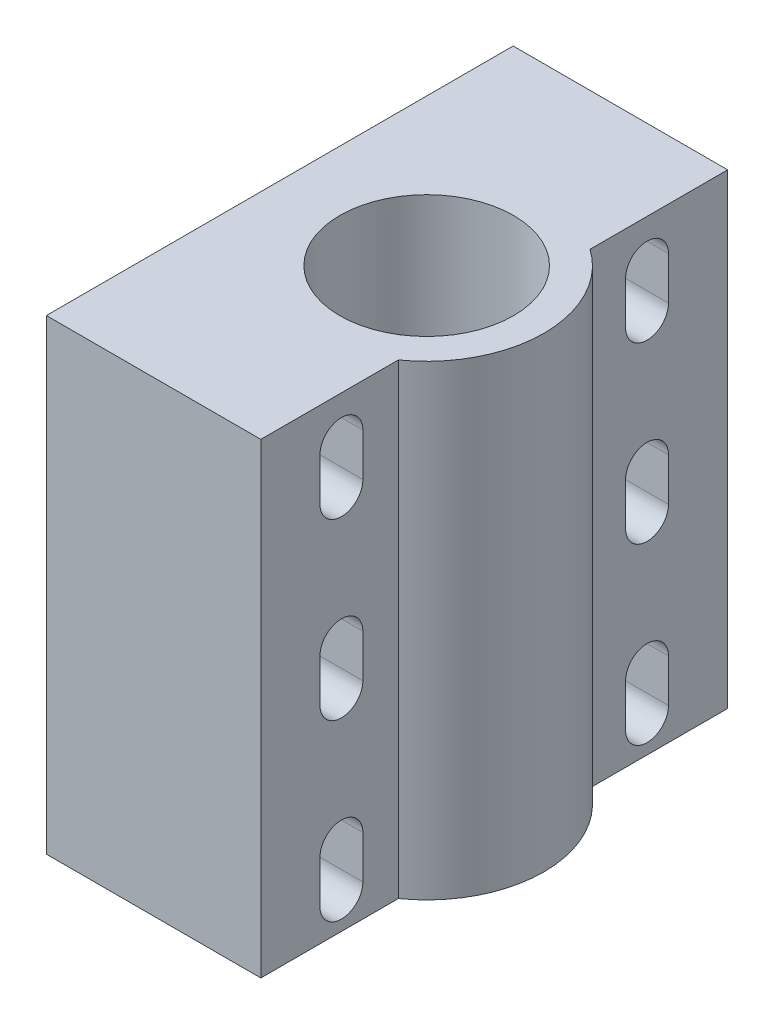
SolidWorks part; units mm, degrees
ref_plane "Front Plane" through (0, 0, 0) normal (0, 0, 1) x (1, 0, 0)
ref_plane "Top Plane" through (0, 0, 0) normal (0, 1, 0) x (1, 0, 0)
ref_plane "Right Plane" through (0, 0, 0) normal (1, 0, 0) x (0, 0, -1)
sketch "Sketch1" plane through (0, 0, 0) normal (0, 0, 1) x (1, 0, 0)
  line L0 (0, 0) -> (0, 6)
  line L1 (0, 6) -> (1.8335, 6)
  line L2 (1.8335, 6) -> (1.8335, 11.5)
  line L3 (1.8335, 11.5) -> (0, 11.5)
  line L4 (0, 11.5) -> (0, 15.5)
  line L5 (0, 15.5) -> (1.8335, 15.5)
  line L6 (1.8335, 15.5) -> (1.8335, 16.5)
  line L7 (-0.1665, 18.5) -> (-3, 18.5)
  line L8 (-3, 18.5) -> (-3, 0)
  line L9 (-3, 0) -> (0, 0)
  line L10 (7.9335, 6) -> (7.9335, 11.5) construction
  line L11 (1.8335, 16.5) -> (-0.1665, 18.5)
  point P9 (1.8335, 18.5)
  dimension "D1" = 5.5
  dimension "D2" = 4
  dimension "D3" = 6.1
  dimension "D4" = 6
  dimension "D5" = 3
  dimension "D6" = 3
revolve "Revolve1" add sketch "Sketch1" angle 360 about L10
sketch "Sketch2" plane through (0, 18.5, 0) normal (0, 1, 0) x (1, 0, 0)
  line L0 (-5.7665, -10.9335) -> (-5.7665, -21.7657)
  line L1 (-5.7665, 10.9335) -> (-5.7665, -10.9335)
  line L2 (-5.7665, -21.7657) -> (14.2335, -21.7657)
  line L3 (14.2335, 8.9359) -> (14.2335, 21.7657)
  line L5 (14.2335, -21.7657) -> (14.2335, -8.9359)
  line L6 (14.2335, 21.7657) -> (-5.7665, 21.7657)
  line L7 (-5.7665, 21.7657) -> (-5.7665, 10.9335)
  circle A1 centre (7.9335, 0) radius 8.1 construction
  arc A2 (14.2335, 8.9359) -> (14.2335, -8.9359) centre (7.9335, 0) ccw
  point P0 (-5.7665, 0)
  dimension "D1" = 13.7
  dimension "D2" = 20
extrude "Boss-Extrude1" add sketch "Sketch2" against normal up to surface (18.5 mm away) and the other way blind 25 up to face at (7.9335, 0, -7.9335)
sketch "Sketch3" plane through (-5.7665, 0, 0) normal (-1, 0, 0) x (0, 0, 1)
  line L0 (0, 43.5) -> (0, 0) construction
  line L1 (-21.7657, 43.5) -> (21.7657, 43.5) construction
  line L2 (21.7657, 0) -> (-21.7657, 0) construction
  line L3 (0, 37.5) -> (-14.25, 37.5) construction
  line L4 (0, 37.5) -> (14.25, 37.5) construction
  line L5 (-14.25, 39.5) -> (-14.25, 35.5) construction
  line L6 (-12.25, 39.5) -> (-12.25, 35.5)
  line L7 (-16.25, 39.5) -> (-16.25, 35.5)
  line L8 (14.25, 39.5) -> (14.25, 35.5) construction
  line L9 (16.25, 39.5) -> (16.25, 35.5)
  line L10 (12.25, 39.5) -> (12.25, 35.5)
  line L11 (-14.25, 23.25) -> (-14.25, 19.25) construction
  line L12 (-12.25, 23.25) -> (-12.25, 19.25)
  line L13 (-16.25, 23.25) -> (-16.25, 19.25)
  line L14 (14.25, 23.25) -> (14.25, 19.25) construction
  line L15 (16.25, 23.25) -> (16.25, 19.25)
  line L16 (12.25, 23.25) -> (12.25, 19.25)
  line L17 (-14.25, 7) -> (-14.25, 3) construction
  line L18 (-12.25, 7) -> (-12.25, 3)
  line L19 (-16.25, 7) -> (-16.25, 3)
  line L20 (14.25, 7) -> (14.25, 3) construction
  line L21 (16.25, 7) -> (16.25, 3)
  line L22 (12.25, 7) -> (12.25, 3)
  arc A0 (-12.25, 39.5) -> (-16.25, 39.5) centre (-14.25, 39.5) ccw
  arc A1 (-16.25, 35.5) -> (-12.25, 35.5) centre (-14.25, 35.5) ccw
  arc A2 (16.25, 39.5) -> (12.25, 39.5) centre (14.25, 39.5) ccw
  arc A3 (12.25, 35.5) -> (16.25, 35.5) centre (14.25, 35.5) ccw
  arc A4 (-12.25, 23.25) -> (-16.25, 23.25) centre (-14.25, 23.25) ccw
  arc A5 (-16.25, 19.25) -> (-12.25, 19.25) centre (-14.25, 19.25) ccw
  arc A6 (16.25, 23.25) -> (12.25, 23.25) centre (14.25, 23.25) ccw
  arc A7 (12.25, 19.25) -> (16.25, 19.25) centre (14.25, 19.25) ccw
  arc A8 (-12.25, 7) -> (-16.25, 7) centre (-14.25, 7) ccw
  arc A9 (-16.25, 3) -> (-12.25, 3) centre (-14.25, 3) ccw
  arc A10 (16.25, 7) -> (12.25, 7) centre (14.25, 7) ccw
  arc A11 (12.25, 3) -> (16.25, 3) centre (14.25, 3) ccw
  point P11 (-14.25, 37.5)
  point P17 (14.25, 37.5)
  point P27 (-14.25, 21.25)
  point P33 (14.25, 21.25)
  point P41 (-14.25, 5)
  point P47 (14.25, 5)
  dimension "D3" = 2
  dimension "D1" = 28.5
  dimension "D2" = 4
  dimension "D5" = 6
  dimension "D4" = 3
extrude "Cut-Extrude1" cut sketch "Sketch3" against normal blind 50
sketch "Sketch4" plane through (0, 18.5, 0) normal (0, 1, 0) x (1, 0, 0)
  circle A0 centre (7.9335, 0) radius 10.9335
  circle A1 centre (7.9335, 0) radius 8.1
extrude "Boss-Extrude2" add sketch "Sketch4" along normal up to surface (25 mm away) up to face at (4.6945, 43.5, 0)
